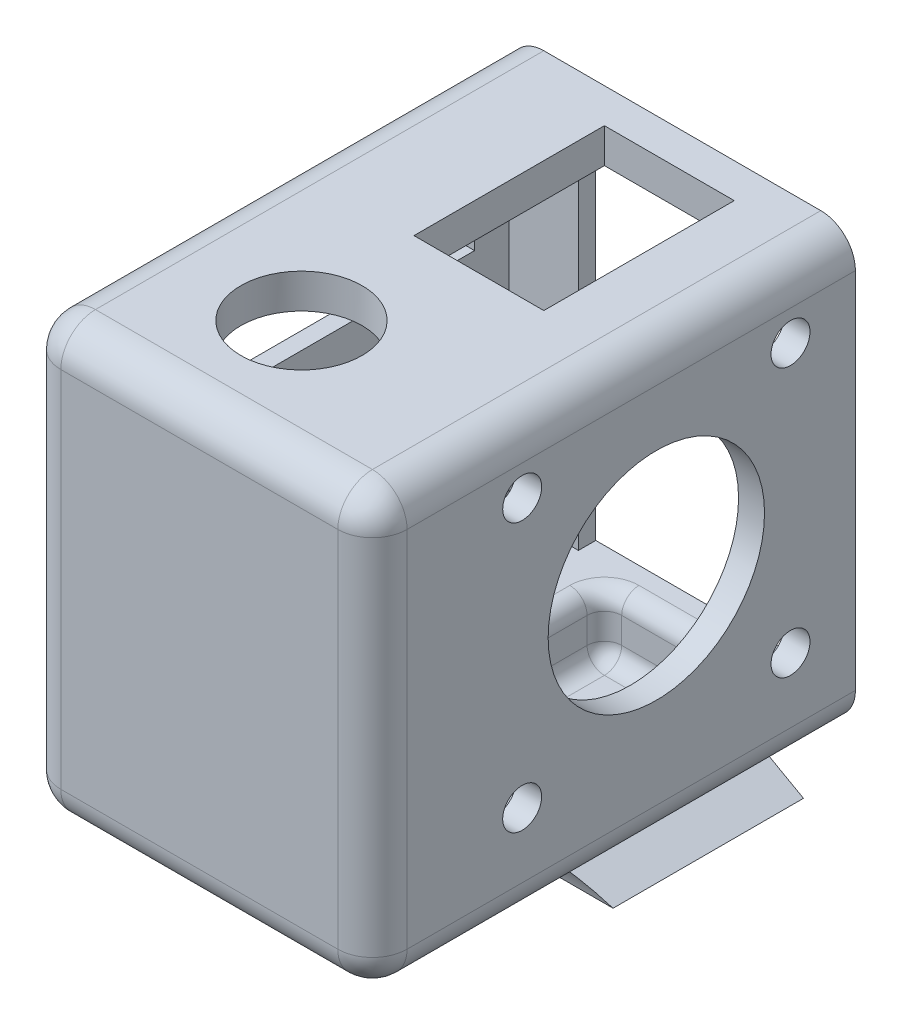
SolidWorks part; units mm, degrees
ref_plane "前视基准面" through (0, 0, 0) normal (0, 0, 1) x (1, 0, 0)
ref_plane "上视基准面" through (0, 0, 0) normal (0, 1, 0) x (1, 0, 0)
ref_plane "右视基准面" through (0, 0, 0) normal (1, 0, 0) x (0, 0, -1)
sketch "草图1" plane through (0, 0, 0) normal (0, 0, 1) x (1, 0, 0)
  line L1 (0, 0) -> (40, 0)
  line L2 (0, 0) -> (0, 50)
  line L3 (0, 50) -> (40, 50)
  line L4 (40, 0) -> (40, 50)
  line L5 (2, 4) -> (37, 4)
  line L6 (2, 4) -> (2, 46)
  line L7 (2, 46) -> (37, 46)
  line L8 (37, 4) -> (37, 46)
  dimension "D1" = 4
  dimension "D2" = 4
  dimension "D3" = 3
  dimension "D4" = 2
  dimension "D5" = 50
  dimension "D6" = 40
extrude "凸台-拉伸1" add sketch "草图1" along normal blind 55
sketch "草图2" plane through (40, 0, 0) normal (1, 0, 0) x (0, 0, -1)
  line L0 (-23, -15.2967) -> (-23, 92.9945) construction
  line L1 (-53.6807, 27) -> (44.2369, 27) construction
  line L3 (-38.5, -14.3438) -> (-38.5, 77.6232) construction
  line L4 (28.2172, 5.5314) -> (28.2172, -24.4686) construction
  line L5 (-55, 50) -> (0, 50) construction
  line L6 (0, 0) -> (0, 50) construction
  circle A2 centre (-7.5, 42.5) radius 2.25
  circle A4 centre (-23, 27) radius 12.5
  circle A5 centre (-7.5, 11.5) radius 2.25
  circle A6 centre (-38.5, 11.5) radius 2.25
  circle A7 centre (-38.5, 42.5) radius 2.25
  dimension "D2" = 31
  dimension "D3" = 25
  dimension "D1" = 31
  dimension "D4" = 23
  dimension "D5" = 23
extrude "切除-拉伸1" cut sketch "草图2" against normal up to next
sketch "草图3" plane through (0, 50, 0) normal (0, 1, 0) x (1, 0, 0)
  line L2 (40, -23) -> (0, -23) construction
  line L3 (40, -55) -> (40, 0) construction
  line L4 (0, -55) -> (0, 0) construction
  line L5 (40, 0) -> (0, 0) construction
  circle A0 centre (17, -41) radius 7
  dimension "D1" = 14
  dimension "D4" = 18
  dimension "D2" = 23
  dimension "D3" = 23
extrude "切除-拉伸2" cut sketch "草图3" against normal through all
sketch "草图4" plane through (0, 0, 0) normal (0, 0, -1) x (-1, 0, 0)
  line L2 (-32, -4) -> (-37, -6.8)
  line L3 (-37, -6.8) -> (-8, -6.8)
  line L5 (-22.5, 6.0519) -> (-22.5, -8.9476) construction
  line L6 (-13, -4) -> (-8, -6.8)
  line L7 (-32, -4) -> (-32, 0)
  line L8 (-37, 4) -> (-37, 46) construction
  line L9 (0, 0) -> (-40, 0) construction
  line L10 (-32, 0) -> (-13, 0)
  line L11 (-13, 0) -> (-13, -4)
  point P4 (0, 0)
  point P9 (-22.5, -6.8)
  point P14 (0, 0)
  point P15 (-22.5, 6.0519)
  point P16 (-26.4392, -4.0369)
  dimension "D1" = 9.5
  dimension "D2" = 14.5
  dimension "D3" = 2.8
  dimension "D4" = 4
extrude "凸台-拉伸2" add sketch "草图4" against normal blind 22 from offset 3 offset against normal yes
fillet "圆角1" radius 10 1 edges at (22.5, 0, 25)
sketch "草图5" plane through (0, 4, 0) normal (0, 1, 0) x (1, 0, 0)
  line L2 (30, -4) -> (15, -4)
  line L3 (30, -4) -> (30, -26)
  line L4 (30, -26) -> (15, -26)
  line L5 (15, -4) -> (15, -26)
  line L6 (22.5, -4) -> (22.5, -33.9561) construction
  line L7 (37, -55) -> (37, 0) construction
  line L8 (2, 0) -> (37, 0) construction
  dimension "D1" = 14.5
  dimension "D2" = 7.5
  dimension "D3" = 4
  dimension "D4" = 22
extrude "切除-拉伸3" cut sketch "草图5" against normal blind 7 and the other way through all
sketch "草图6" plane through (0, 0, 55) normal (0, 0, 1) x (1, 0, 0)
  line L1 (0, 0) -> (40, 0)
  line L2 (0, 0) -> (0, 50)
  line L3 (0, 50) -> (40, 50)
  line L4 (40, 0) -> (40, 50)
extrude "凸台-拉伸3" add sketch "草图6" along normal blind 0.8
sketch "草图7" plane through (0, -3, 0) normal (0, 1, 0) x (1, 0, 0)
  line L0 (22.5, -4) -> (22.5, -25.9388) construction
  line L1 (30, -4) -> (15, -4) construction
  circle A0 centre (22.5, -8) radius 2
  circle A1 centre (22.5, -18) radius 2
  dimension "D2" = 4
  dimension "D3" = 4
  dimension "D1" = 10
  dimension "D4" = 4
extrude "切除-拉伸4" cut sketch "草图7" against normal blind 10
sketch "草图8" plane through (0, 0, 0) normal (0, 0, -1) x (-1, 0, 0)
  line L0 (0, 32) -> (0, 28)
  line L1 (0, 50) -> (0, 0) construction
  line L2 (0, 28) -> (11.4757, 24.4915)
  line L3 (0, 32) -> (11.4757, 28.4915)
  line L4 (11.4757, 24.4915) -> (11.4757, 28.4915)
  dimension "D1" = 18
  dimension "D2" = 4
  dimension "D3" = 73
  dimension "D4" = 12
extrude "凸台-拉伸4" add sketch "草图8" against normal blind 44
sketch "草图9" plane through (0, 50, 0) normal (0, 1, 0) x (1, 0, 0)
  line L0 (-11.4757, -44) -> (-11.4757, 0) construction
  line L1 (-11.4757, -36) -> (0, -36)
  line L2 (-11.4757, -36) -> (-11.4757, -8)
  line L3 (-11.4757, -8) -> (0, -8)
  line L4 (0, -36) -> (0, -8)
  line L5 (0, -55.8) -> (0, 0) construction
  line L6 (-11.4757, 0) -> (0, 0) construction
  line L7 (-11.4757, -44) -> (0, -44) construction
  dimension "D1" = 8
  dimension "D2" = 8
extrude "切除-拉伸5" cut sketch "草图9" against normal up to next
sketch "草图10" plane through (-8.9471, 29.2646, 0) normal (-0.2924, 0.9563, 0) x (0.9563, 0.2924, 0)
  line L0 (-2.6441, 0) -> (9.3559, 0) construction
  line L1 (-2.6441, -8) -> (-2.6441, 0) construction
  line L2 (-2.6441, -44) -> (-2.6441, -36) construction
  line L3 (-2.6441, -44) -> (9.3559, -44) construction
  circle A0 centre (1.3559, -4) radius 1.4
  circle A1 centre (1.3559, -40) radius 1.4
  dimension "D3" = 2.8
  dimension "D4" = 2.8
  dimension "D1" = 4
  dimension "D2" = 4
  dimension "D5" = 4
  dimension "D6" = 4
extrude "切除-拉伸6" cut sketch "草图10" against normal up to next
fillet "圆角2" radius 4 4 edges at (-11.4757, 26.4915, 0) (-11.4757, 26.4915, 44) (-11.4757, 26.4915, 8) (-11.4757, 26.4915, 36)
sketch "草图11" plane through (0, 0, 0) normal (-1, 0, 0) x (0, 0, 1)
  line L0 (0, 28) -> (0, 0) construction
  line L1 (6, 6) -> (48, 6)
  line L2 (6, 6) -> (6, 21)
  line L3 (6, 21) -> (48, 21)
  line L4 (48, 6) -> (48, 21)
  line L5 (6, 32) -> (48, 32)
  line L6 (6, 32) -> (6, 44)
  line L7 (6, 44) -> (48, 44)
  line L8 (48, 32) -> (48, 44)
  line L9 (55.8, 0) -> (0, 0) construction
  line L10 (55.8, 50) -> (0, 50) construction
  dimension "D1" = 6
  dimension "D2" = 6
  dimension "D3" = 6
  dimension "D4" = 12
  dimension "D5" = 15
  dimension "D6" = 42
extrude "切除-拉伸7" cut sketch "草图11" against normal up to next
sketch "草图12" plane through (0, 0, 0) normal (0, 0, -1) x (-1, 0, 0)
  line L0 (-40, 50) -> (0, 50) construction
  line L1 (0, 0) -> (-10, 0)
  line L2 (0, 0) -> (0, 50)
  line L3 (0, 50) -> (-10, 50)
  line L4 (-10, 0) -> (-10, 50)
  line L5 (0, 25) -> (-31.4099, 25) construction
  circle A0 centre (-6, 42) radius 1.4
  circle A1 centre (-6, 8) radius 1.4
  dimension "D2" = 2.8
  dimension "D3" = 34
  dimension "D4" = 6
  dimension "D1" = 10
extrude "凸台-拉伸5" add sketch "草图12" against normal blind 2
fillet "圆角3" radius 4 8 edges at (0, 25, 55.8) (40, 25, 55.8) (20, 0, 55.8) (20, 50, 55.8) (0, 50, 27.9) (0, 0, 27.9) (40, 50, 27.9) (40, 0, 27.9)
fillet "圆角4" radius 2 23 edges at (19.5, 4, 55) (37, 25, 55) (19.5, 46, 55) (2, 25, 55) (2, 4, 28.5) (37, 46, 27.5) (2, 46, 28.5) (37, 4, 27.5) (13, 0, 18.7371) (32, 0, 18.7371) (22.5, 0, 3) (30, 4, 15) (15, 4, 15) (22.5, 4, 4) (30, 0.5, 4) (22.5, -3, 4) (15, 0.5, 4) (22.5, 4, 26) (15, 0.5, 26) (22.5, -3, 26) (30, 0.5, 26) (30, -3, 15) (15, -3, 15)
